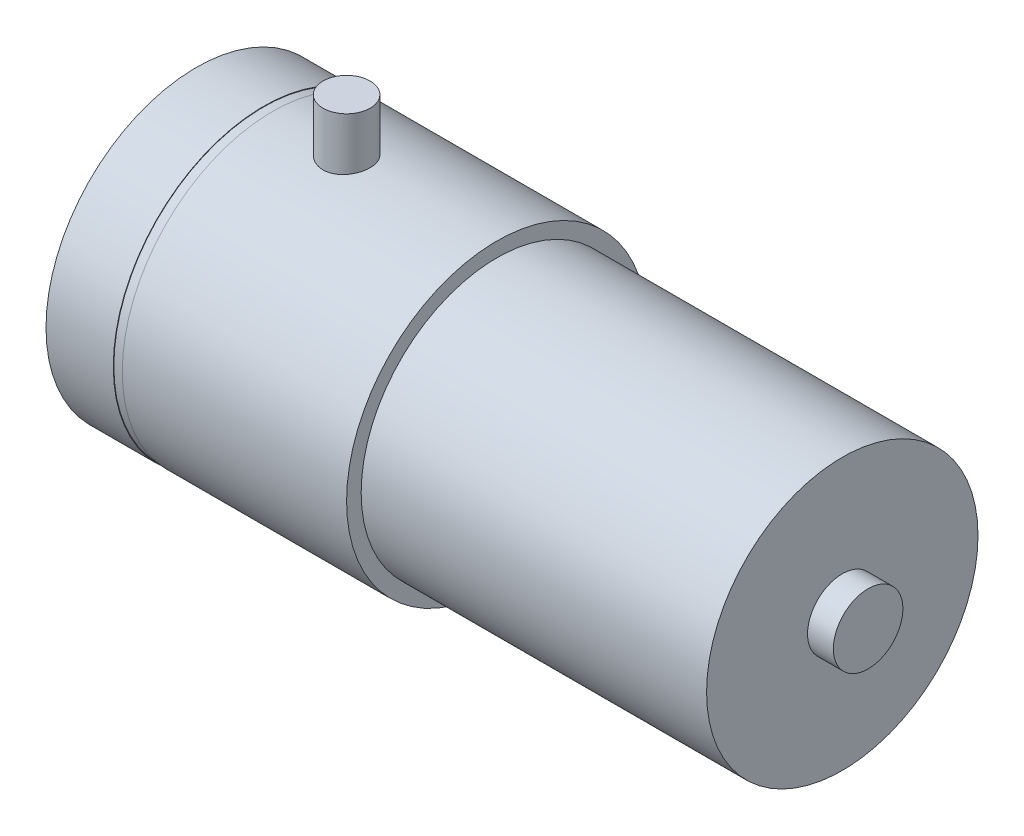
SolidWorks part; units mm, degrees
ref_plane "Plan de face" through (0, 0, 0) normal (0, 0, 1) x (1, 0, 0)
ref_plane "Plan de dessus" through (0, 0, 0) normal (0, 1, 0) x (1, 0, 0)
ref_plane "Plan de droite" through (0, 0, 0) normal (1, 0, 0) x (0, 0, -1)
sketch "Esquisse1" plane through (0, 0, 0) normal (0, 0, 1) x (1, 0, 0)
  line L0 (0, 0) -> (18.7332, 0) construction
  line L1 (-33.6, 0) -> (-33.6, 2.15)
  line L2 (-33.6, 2.15) -> (-26.8, 2.15)
  line L3 (-26.8, 2.15) -> (-26.8, 13.4)
  line L4 (-26.8, 13.4) -> (0, 13.4)
  line L5 (0, 13.4) -> (0, 12.1)
  line L6 (0, 12.1) -> (30.8, 12.1)
  line L7 (30.8, 12.1) -> (30.8, 3.1)
  line L8 (30.8, 3.1) -> (33.1, 3.1)
  line L9 (33.1, 3.1) -> (33.1, 0)
  line L10 (0, 12.1) -> (0, 0) construction
  line L11 (-33.6, 0) -> (33.1, 0)
  point P2 (0, 0)
  dimension "D1" = 2.15
  dimension "D2" = 6.8
  dimension "D3" = 26.8
  dimension "D4" = 57.6
  dimension "D5" = 2.3
  dimension "D6" = 13.4
  dimension "D7" = 12.1
  dimension "D8" = 3.1
revolve "Révolution1" add sketch "Esquisse1" angle 360 about L0
sketch "Esquisse2" plane through (0, 0, 0) normal (0, 1, 0) x (1, 0, 0)
  circle A0 centre (-13.3998, 0) radius 2.1
  dimension "D1" = 4.2
extrude "Boss.-Extru.1" add sketch "Esquisse2" along normal blind 18
sketch "Esquisse3" plane through (-26.8, 0, 0) normal (-1, 0, 0) x (0, 0, 1)
  circle A0 centre (0, 0) radius 13.35
  circle A1 centre (0, 0) radius 13.4 construction
  circle A2 centre (0, 0) radius 13.4
  point P3 (0, 13.35)
  point P7 (0, 13.4)
  dimension "D1" = 0.05
extrude "Enlèv. mat.-Extru.1" cut sketch "Esquisse3" against normal blind 0.8 from offset 6 offset against normal yes
